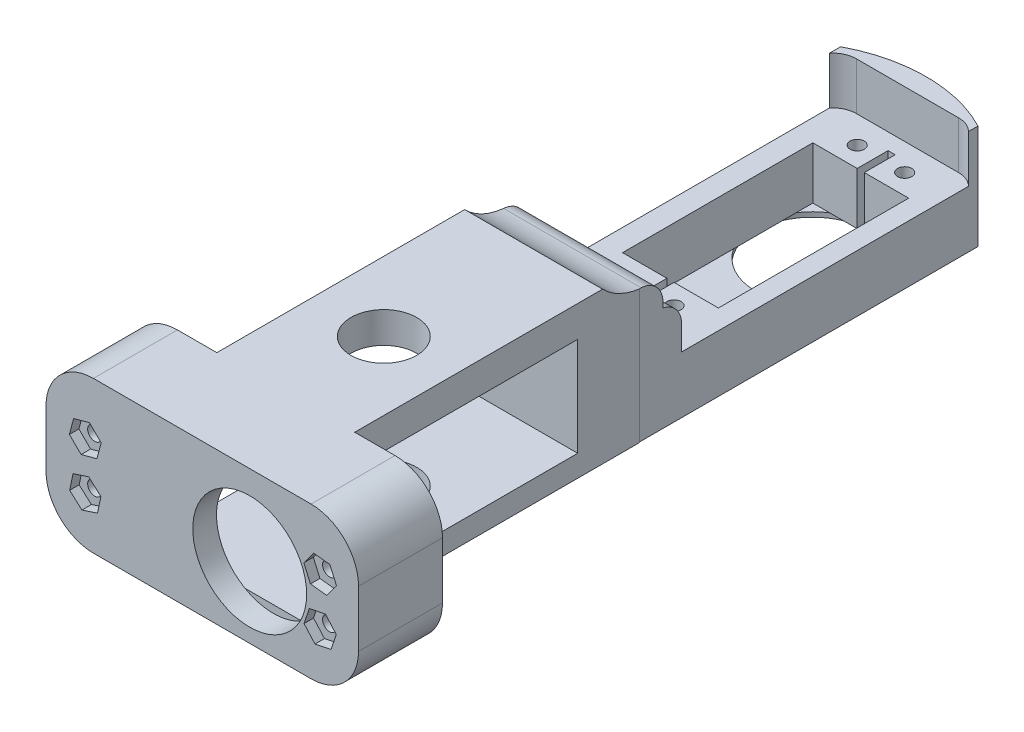
SolidWorks part; units mm, degrees
ref_plane "前视基准面" through (0, 0, 0) normal (0, 0, 1) x (1, 0, 0)
ref_plane "上视基准面" through (0, 0, 0) normal (0, 1, 0) x (1, 0, 0)
ref_plane "右视基准面" through (0, 0, 0) normal (1, 0, 0) x (0, 0, -1)
sketch "草图1" plane through (0, 0, 0) normal (0, 0, 1) x (1, 0, 0)
  line L0 (-20.4, -0.75) -> (-20.4, -10.4)
  line L1 (-30, 20) -> (30, 20)
  line L2 (-33, 17) -> (-33, -17)
  line L3 (-30, -20) -> (30, -20)
  line L4 (33, 17) -> (33, -17)
  line L5 (-33, 20) -> (33, -20) construction
  line L6 (-33, -20) -> (33, 20) construction
  line L7 (-20.4, 10.4) -> (20.4, 10.4)
  line L8 (-20.4, 10.4) -> (-20.4, 0.75)
  line L9 (-20.4, -10.4) -> (20.4, -10.4)
  line L10 (20.4, 10.4) -> (20.4, 0.75)
  line L11 (-20.4, 10.4) -> (20.4, -10.4) construction
  line L12 (-20.4, -10.4) -> (20.4, 10.4) construction
  line L13 (-28.7182, 0.75) -> (-20.4, 0.75)
  line L14 (-28.7182, 0.75) -> (-28.7182, -0.75)
  line L15 (-28.7182, -0.75) -> (-20.4, -0.75)
  line L17 (20.4, -0.75) -> (20.4, -10.4)
  line L19 (20.4, 0.75) -> (28.3856, 0.75)
  line L21 (20.4, -0.75) -> (28.3856, -0.75)
  line L22 (28.3856, 0.75) -> (28.3856, -0.75)
  arc A0 (-33, -17) -> (-30, -20) centre (-30, -17) ccw
  arc A1 (30, -20) -> (33, -17) centre (30, -17) ccw
  arc A2 (30, 20) -> (33, 17) centre (30, 17) cw
  arc A3 (-30, 20) -> (-33, 17) centre (-30, 17) ccw
  circle A4 centre (-24.65, 5.0883) radius 2.15
  circle A5 centre (-24.65, -4.9117) radius 2.15
  circle A6 centre (24.85, 5.0883) radius 2.15
  circle A7 centre (24.85, -4.9117) radius 2.15
  point P0 (0, 0)
  point P18 (0, 0)
  point P23 (-17.7766, 0.0883)
  point P28 (20.4, 0)
  dimension "D1" = 3
  dimension "D2" = 10
  dimension "D3" = 5
  dimension "D4" = 49.5
  dimension "D5" = 4.25
extrude "凸台-拉伸1" add sketch "草图1" along normal blind 12.7
sketch "草图2" plane through (0, 0, 12.7) normal (0, 0, 1) x (1, 0, 0)
  line L1 (-29.9299, 19.9398) -> (29.9299, 19.9398)
  line L2 (-32.9299, 16.9398) -> (-32.9299, -16.9398)
  line L3 (-29.9299, -19.9398) -> (29.9299, -19.9398)
  line L4 (32.9299, 16.9398) -> (32.9299, -16.9398)
  line L5 (-32.9299, 19.9398) -> (32.9299, -19.9398) construction
  line L6 (-32.9299, -19.9398) -> (32.9299, 19.9398) construction
  arc A0 (-29.9299, -19.9398) -> (-32.9299, -16.9398) centre (-29.9299, -16.9398) cw
  arc A1 (32.9299, -16.9398) -> (29.9299, -19.9398) centre (29.9299, -16.9398) cw
  arc A2 (29.9299, 19.9398) -> (32.9299, 16.9398) centre (29.9299, 16.9398) cw
  arc A3 (-29.9299, 19.9398) -> (-32.9299, 16.9398) centre (-29.9299, 16.9398) ccw
  circle A4 centre (10, 0) radius 12
  point P0 (0, 0)
  dimension "D1" = 3
  dimension "D2" = 10
extrude "凸台-拉伸3" add sketch "草图2" along normal blind 5 contours L2 A0 L3 A1 L4 A2 L1 A3 | A4
sketch "草图3" plane through (0, 0, 0) normal (0, 0, -1) x (-1, 0, 0)
  line L1 (-30, 19.9598) -> (30, 19.9598)
  line L2 (-33, 16.9598) -> (-33, -16.9598)
  line L3 (-30, -19.9598) -> (30, -19.9598)
  line L4 (33, 16.9598) -> (33, -16.9598)
  line L5 (-33, 19.9598) -> (33, -19.9598) construction
  line L6 (-33, -19.9598) -> (33, 19.9598) construction
  line L7 (-33, 10.2) -> (33, 10.2)
  line L8 (-33, 10.2) -> (-33, -10.2)
  line L9 (-33, -10.2) -> (33, -10.2)
  line L10 (33, 10.2) -> (33, -10.2)
  line L11 (-33, 10.2) -> (33, -10.2) construction
  line L12 (-33, -10.2) -> (33, 10.2) construction
  arc A0 (-33, -16.9598) -> (-30, -19.9598) centre (-30, -16.9598) ccw
  arc A1 (33, -16.9598) -> (30, -19.9598) centre (30, -16.9598) cw
  arc A2 (33, 16.9598) -> (30, 19.9598) centre (30, 16.9598) ccw
  arc A3 (-30, 19.9598) -> (-33, 16.9598) centre (-30, 16.9598) ccw
  point P1 (0, 0)
  point P18 (0, 0)
  line M14 (33, -17) -> (33, 17)
  line M18 (-33, 17) -> (-33, -17)
  line M21 (-20.4, -10.4) -> (-20.4, -0.75)
  line M25 (-20.4, 0.75) -> (-20.4, 10.4)
  line M26 (-20.4, 10.4) -> (20.4, 10.4)
  line M27 (20.4, 10.4) -> (20.4, 0.75)
  line M31 (20.4, -0.75) -> (20.4, -10.4)
  line M32 (20.4, -10.4) -> (-20.4, -10.4)
  dimension "D1" = 3
  dimension "D2" = 3
  dimension "D3" = 20.4
extrude "凸台-拉伸4" add sketch "草图3" along normal blind 50 contours L1 A3 L7 L4 A2 M18 M25 M26 M27 | A1 L9 A0 L3 M14 M31 M32 M21 M18 region at (0, 15.1159, 0) region at (0, -15.1159, 0)
sketch "草图4" plane through (0, 0, -50) normal (0, 0, -1) x (-1, 0, 0)
  line L2 (-33, 13.0402) -> (33, 13.0402)
  line L3 (-30, 19.9598) -> (30, 19.9598)
  line L4 (-33, 16.9598) -> (-33, -16.9598)
  line L5 (-30, -19.9598) -> (30, -19.9598)
  line L6 (33, 16.9598) -> (33, -16.9598)
  line L7 (-33, 19.9598) -> (33, -19.9598) construction
  line L8 (-33, -19.9598) -> (33, 19.9598) construction
  line L9 (-30, 19.9598) -> (30, 19.9598) construction
  line L10 (33, 10.2) -> (33, 16.9598) construction
  arc A0 (30, 19.9598) -> (33, 16.9598) centre (30, 16.9598) cw
  arc A1 (33, -16.9598) -> (30, -19.9598) centre (30, -16.9598) cw
  arc A2 (-33, -16.9598) -> (-30, -19.9598) centre (-30, -16.9598) ccw
  arc A3 (-30, 19.9598) -> (-33, 16.9598) centre (-30, 16.9598) ccw
  point P4 (0, 0)
  line M11 (-33, 16.9598) -> (-33, 10.2)
  line M12 (-33, 10.2) -> (-20.4, 10.2)
  line M13 (-20.4, 10.2) -> (-20.4, 10.4)
  line M14 (-20.4, 10.4) -> (20.4, 10.4)
  line M15 (20.4, 10.4) -> (20.4, 10.2)
  line M16 (20.4, 10.2) -> (33, 10.2)
  line M17 (33, 10.2) -> (33, 16.9598)
  dimension "D1" = 3
  dimension "D2" = 33
extrude "凸台-拉伸5" add sketch "草图4" along normal blind 60 and the other way blind 5 contours L4 A2 L5 A1 L6 M16 M15 M14 M13 M12 | L2 M11 M12 M13 M14 M15 M16 M17 region at (0, 11.6802, -50) region at (0, -4.7899, -50)
sketch "草图5" plane through (33, 0, 0) normal (1, 0, 0) x (0, 0, -1)
  line L0 (50, 19.9598) -> (50, 13.0402)
  line L1 (50, 19.9598) -> (60.4504, 19.9598)
  line L2 (50, 13.0402) -> (60.4504, 13.0402)
  line L3 (60.4504, 19.9598) -> (60.4504, 13.0402)
  spline S0 degree 2 poles (50, 19.9598) (53.4679, 13.8563) (60.4504, 13.0402) knots 0 0 0 1 1 1
extrude "凸台-拉伸6" add sketch "草图5" against normal blind 66 contours S0 L0 region at (33, 14.9849, -52.6781)
sketch "草图6" plane through (0, 0, -45) normal (0, 0, 1) x (1, 0, 0)
  line L0 (-29.9299, 19.9398) -> (29.9299, 19.9398) construction
  line L1 (-37.9014, 22.667) -> (37.9014, 22.667)
  line L2 (-37.9014, 22.667) -> (-37.9014, -22.667)
  line L3 (-37.9014, -22.667) -> (37.9014, -22.667)
  line L4 (37.9014, 22.667) -> (37.9014, -22.667)
  line L5 (-37.9014, 22.667) -> (37.9014, -22.667) construction
  line L6 (-37.9014, -22.667) -> (37.9014, 22.667) construction
  line L7 (-29.9299, 19.9398) -> (29.9299, 19.9398)
  line L8 (-32.9299, 16.9398) -> (-32.9299, -16.9398)
  line L9 (-29.9299, -19.9398) -> (29.9299, -19.9398)
  line L10 (32.9299, 16.9398) -> (32.9299, -16.9398)
  line L11 (-32.9299, 19.9398) -> (32.9299, -19.9398) construction
  line L12 (-32.9299, -19.9398) -> (32.9299, 19.9398) construction
  line L13 (-32.9299, 16.9398) -> (-32.9299, -16.9398) construction
  arc A0 (29.9299, 19.9398) -> (32.9299, 16.9398) centre (29.9299, 16.9398) cw
  arc A1 (32.9299, -16.9398) -> (29.9299, -19.9398) centre (29.9299, -16.9398) cw
  arc A2 (-29.9299, -19.9398) -> (-32.9299, -16.9398) centre (-29.9299, -16.9398) cw
  arc A3 (-32.9299, 16.9398) -> (-29.9299, 19.9398) centre (-29.9299, 16.9398) cw
  point P0 (0, 0)
  point P6 (0, 0)
  dimension "D1" = 3
extrude "切除-拉伸2" cut sketch "草图6" against normal blind 102
sketch "草图8" plane through (0, 13.0402, 0) normal (0, 1, 0) x (1, 0, 0)
  line L0 (-32.9299, 110) -> (32.9299, 110)
  arc A0 (-32.9299, 110) -> (32.9299, 110) centre (0, 108.1219) cw
extrude "凸台-拉伸7" add sketch "草图8" against normal blind 33
sketch "草图9" plane through (0, 13.0402, 0) normal (0, 1, 0) x (1, 0, 0)
  line L1 (-10.0231, 120.9982) -> (10.1769, 120.9982)
  line L2 (-10.0231, 120.9982) -> (-10.0231, 80.8982)
  line L3 (-10.0231, 80.8982) -> (10.1769, 80.8982)
  line L4 (10.1769, 120.9982) -> (10.1769, 80.8982)
  line L5 (-10.0231, 120.9982) -> (10.1769, 80.8982) construction
  line L6 (-10.0231, 80.8982) -> (10.1769, 120.9982) construction
  line L7 (-0.6731, 127.4982) -> (0.8269, 127.4982)
  line L8 (-0.6731, 127.4982) -> (-0.6731, 114.4982)
  line L9 (-0.6731, 114.4982) -> (0.8269, 114.4982)
  line L10 (0.8269, 127.4982) -> (0.8269, 114.4982)
  line L11 (-0.6731, 127.4982) -> (0.8269, 114.4982) construction
  line L12 (-0.6731, 114.4982) -> (0.8269, 127.4982) construction
  line L13 (-0.6731, 87.3982) -> (0.8269, 87.3982)
  line L14 (-0.6731, 87.3982) -> (-0.6731, 74.3982)
  line L15 (-0.6731, 74.3982) -> (0.8269, 74.3982)
  line L16 (0.8269, 87.3982) -> (0.8269, 74.3982)
  line L17 (-0.6731, 87.3982) -> (0.8269, 74.3982) construction
  line L18 (-0.6731, 74.3982) -> (0.8269, 87.3982) construction
  circle A0 centre (-4.9231, 125.2482) radius 2.02
  circle A1 centre (5.0769, 125.2482) radius 2.02
  circle A2 centre (-4.9231, 76.6482) radius 2.02
  circle A3 centre (5.0769, 76.6482) radius 2.02
  point P0 (0.0769, 100.9482)
  point P13 (0.0769, 120.9982)
  point P18 (0.0769, 80.8982)
  dimension "D1" = 10
  dimension "D2" = 5
  dimension "D3" = 24.3
  dimension "D4" = 24.3
  dimension "D5" = 40.1
  dimension "D6" = 1.5
  dimension "D7" = 1.5
extrude "切除-拉伸4" cut sketch "草图9" against normal blind 27 contours L13 L16 L3 L4 L1 L10 L9 L8 L2 L14 | A0 | A1 | L10 L7 L8 L1 | L10 L1 L8 L9 | L16 L13 L14 L3 | L16 L3 L14 L15 | A3 | A2 region at (0.0769, 13.0402, -100.9482) region at (0.0769, 13.0402, -124.2482) region at (0.0769, 13.0402, -117.7482) region at (0.0769, 13.0402, -84.1482) region at (0.0769, 13.0402, -77.6482) region at (-4.9231, 13.0402, -125.2482) region at (5.0769, 13.0402, -125.2482) region at (-4.9231, 13.0402, -76.6482) region at (5.0769, 13.0402, -76.6482)
sketch "草图11" plane through (0, 13.0402, 0) normal (0, 1, 0) x (1, 0, 0)
  line L1 (-10.7869, 130.9218) -> (10.7869, 130.9218)
  line L2 (-15.7869, 125.9218) -> (-15.7869, 68.999)
  line L3 (-15.7869, 68.999) -> (15.7869, 68.999)
  line L4 (15.7869, 125.9218) -> (15.7869, 68.999)
  line L5 (-15.7869, 130.9218) -> (15.7869, 68.999) construction
  line L6 (-15.7869, 68.999) -> (15.7869, 130.9218) construction
  arc A0 (-10.7869, 130.9218) -> (-15.7869, 125.9218) centre (-10.7869, 125.9218) ccw
  arc A1 (10.7869, 130.9218) -> (15.7869, 125.9218) centre (10.7869, 125.9218) cw
  point P0 (0, 99.9604)
  dimension "D1" = 5
extrude "切除-拉伸5" cut sketch "草图11" against normal blind 16
sketch "草图12" plane through (0, 13.0402, 0) normal (0, 1, 0) x (1, 0, 0)
  line L0 (-25.4565, 110.6309) -> (25.4565, 110.6309)
  line L1 (-25.4565, 110.6309) -> (25.4565, 110.6309)
  line L2 (-25.4565, 110.6309) -> (-25.4565, 65.0871)
  line L3 (-25.4565, 65.0871) -> (25.4565, 65.0871)
  line L4 (25.4565, 110.6309) -> (25.4565, 65.0871)
  line L5 (-25.4565, 110.6309) -> (25.4565, 65.0871) construction
  line L6 (-25.4565, 65.0871) -> (25.4565, 110.6309) construction
  arc A0 (-25.4565, 110.6309) -> (25.4565, 110.6309) centre (0, 110.6309) cw
  point P0 (0, 87.859)
  arc M5 (10.7869, 130.9218) -> (15.7869, 125.9218) centre (10.7869, 125.9218) cw
  line M6 (15.7869, 125.9218) -> (15.7869, 68.999)
  line M7 (15.7869, 68.999) -> (-15.7869, 68.999)
  line M8 (-15.7869, 68.999) -> (-15.7869, 125.9218)
  arc M9 (-15.7869, 125.9218) -> (-10.7869, 130.9218) centre (-10.7869, 125.9218) cw
  line M10 (-10.7869, 130.9218) -> (10.7869, 130.9218)
extrude "切除-拉伸7" cut sketch "草图12" against normal blind 6 contours L4 L0 L2 L3 M6 M7 M8 | A0 L0 M8 M9 M10 M5 M6 region at (0, 13.0402, -135.5181) region at (-20.6217, 13.0402, -109.9478)
sketch "草图13" plane through (0, -13.9598, 0) normal (0, 1, 0) x (1, 0, 0)
  line L0 (0.8269, 80.8982) -> (10.1769, 80.8982) construction
  circle A0 centre (0, 110.8982) radius 12
  dimension "D1" = 30
extrude "切除-拉伸8" cut sketch "草图13" against normal blind 80
sketch "草图14" plane through (0, 0, 17.7) normal (0, 0, 1) x (1, 0, 0)
  line L0 (-29.9299, 19.9398) -> (29.9299, 19.9398) construction
  line L1 (-29.9299, 19.9398) -> (29.9299, 19.9398)
  line L2 (-32.9299, 16.9398) -> (-32.9299, -16.9398)
  line L3 (-29.9299, -19.9398) -> (29.9299, -19.9398)
  line L4 (32.9299, 16.9398) -> (32.9299, -16.9398)
  line L5 (-32.9299, 19.9398) -> (32.9299, -19.9398) construction
  line L6 (-32.9299, -19.9398) -> (32.9299, 19.9398) construction
  line L7 (-32.9299, 16.9398) -> (-32.9299, -16.9398) construction
  line L9 (-36.1294, 24.0704) -> (36.1294, 24.0704)
  line L10 (-36.1294, 24.0704) -> (-36.1294, -24.0704)
  line L11 (-36.1294, -24.0704) -> (36.1294, -24.0704)
  line L12 (36.1294, 24.0704) -> (36.1294, -24.0704)
  line L13 (-36.1294, 24.0704) -> (36.1294, -24.0704) construction
  line L14 (-36.1294, -24.0704) -> (36.1294, 24.0704) construction
  arc A0 (29.9299, 19.9398) -> (32.9299, 16.9398) centre (29.9299, 16.9398) cw
  arc A1 (29.9299, -19.9398) -> (32.9299, -16.9398) centre (29.9299, -16.9398) ccw
  arc A2 (-29.9299, -19.9398) -> (-32.9299, -16.9398) centre (-29.9299, -16.9398) cw
  arc A3 (-29.9299, 19.9398) -> (-32.9299, 16.9398) centre (-29.9299, 16.9398) ccw
  point P0 (0, 0)
  point P22 (0, 0)
  dimension "D1" = 3
extrude "切除-拉伸9" cut sketch "草图14" against normal blind 146
sketch "草图15" plane through (0, 0, 17.7) normal (0, 0, 1) x (1, 0, 0)
  line L1 (-27, 15) -> (27, 15)
  line L2 (-30, 12) -> (-30, -12)
  line L3 (-27, -15) -> (27, -15)
  line L4 (30, 12) -> (30, -12)
  line L5 (-30, 15) -> (30, -15) construction
  line L6 (-30, -15) -> (30, 15) construction
  line L7 (-36.3575, 21.962) -> (36.3575, 21.962)
  line L8 (-36.3575, 21.962) -> (-36.3575, -21.962)
  line L9 (-36.3575, -21.962) -> (36.3575, -21.962)
  line L10 (36.3575, 21.962) -> (36.3575, -21.962)
  line L11 (-36.3575, 21.962) -> (36.3575, -21.962) construction
  line L12 (-36.3575, -21.962) -> (36.3575, 21.962) construction
  arc A0 (27, 15) -> (30, 12) centre (27, 12) cw
  arc A1 (30, -12) -> (27, -15) centre (27, -12) cw
  arc A2 (-27, -15) -> (-30, -12) centre (-27, -12) cw
  arc A3 (-30, 12) -> (-27, 15) centre (-27, 12) cw
  point P0 (0, 0)
  point P18 (0, 0)
  dimension "D1" = 3
sketch "草图18" plane through (0, 0, 0) normal (0, 0, -1) x (-1, 0, 0)
  circle A0 centre (-24.85, 5.0883) radius 2.15
  circle A1 centre (-24.85, 5.0883) radius 2.15 construction
  circle A2 centre (-24.85, 5.0883) radius 1.5
  circle A3 centre (-24.85, -4.9117) radius 2.15
  circle A4 centre (-24.85, -4.9117) radius 2.15 construction
  circle A5 centre (-24.85, -4.9117) radius 1.5
  circle A6 centre (24.65, 5.0883) radius 2.15
  circle A7 centre (24.65, 5.0883) radius 1.5
  circle A8 centre (24.65, -4.9117) radius 2.15
  circle A9 centre (24.65, -4.9117) radius 1.5
extrude "凸台-拉伸8" add sketch "草图18" against normal blind 14
sketch "草图19" plane through (0, 0, 0) normal (0, 0, -1) x (-1, 0, 0)
  circle A0 centre (-24.85, 5.0883) radius 1.5
  circle A1 centre (-24.85, -4.9117) radius 1.5
  circle A2 centre (24.65, 5.0883) radius 1.5
  circle A3 centre (24.65, -4.9117) radius 1.5
extrude "切除-拉伸14" cut sketch "草图19" against normal blind 25
sketch "草图21" plane through (0, 13.0402, 0) normal (0, 1, 0) x (1, 0, 0)
  line L0 (-41.7762, 142.5299) -> (39.2123, 142.5299)
  line L1 (-41.7762, 142.5299) -> (-41.7762, 60.0333)
  line L2 (39.2123, 142.5299) -> (39.2123, 60.0333)
  line L3 (-41.7762, 60.0333) -> (39.2123, 60.0333)
  line L4 (-14.6296, 60.0333) -> (-14.6296, 131.4637)
  line L5 (-14.6296, 60.0333) -> (14.3193, 60.0333)
  line L7 (14.3193, 60.0333) -> (14.3193, 131.4637)
  arc A0 (25.4565, 110.6309) -> (-25.4565, 110.6309) centre (0, 110.6309) ccw construction
  arc A1 (-14.6296, 131.4637) -> (14.3193, 131.4637) centre (-0.1552, 103.7858) cw
  line M5 (25.4565, 110.6309) -> (25.4565, 65.0871)
  line M6 (25.4565, 65.0871) -> (-25.4565, 65.0871)
  line M7 (-25.4565, 65.0871) -> (-25.4565, 110.6309)
  arc M8 (-25.4565, 110.6309) -> (25.4565, 110.6309) centre (0, 110.6309) cw
  arc M10 (32.9299, 110) -> (-32.9299, 110) centre (0, 108.1219) ccw
  line M12 (-32.9299, 60.4504) -> (32.9299, 60.4504)
extrude "切除-拉伸17" cut sketch "草图21" against normal blind 39 contours L7 L4 M12 M10 M6 M7 M8 M5 | L4 M6 M8 M7 | L7 L3 L2 L0 L1 L4 M12 M10 | A1 L7 M8 M6 M5 region at (-1.2819, 13.0402, -141.3738) region at (-19.8019, 13.0402, -95.3565) region at (19.0175, 13.0402, -96.7175)
sketch "草图24" plane through (0, 19.9398, 0) normal (0, 1, 0) x (1, 0, 0)
  line L0 (-14.6296, 60.4504) -> (-29.9299, 0)
  line L1 (-29.9299, -17.7) -> (-29.9299, 50.0114) construction
  line L2 (-29.9299, 0) -> (-48.0566, 0)
  line L3 (-48.0566, 0) -> (-48.0566, 60.4504)
  line L4 (-48.0566, 60.4504) -> (-14.6296, 60.4504)
  line L5 (14.3193, 60.4504) -> (58.3545, 60.4504)
  line L6 (58.3545, 60.4504) -> (58.3545, 0)
  line L7 (58.3545, 0) -> (29.9299, 0)
  line L8 (29.9299, -17.7) -> (29.9299, 50.0114) construction
  line L9 (29.9299, 0) -> (14.3193, 60.4504)
extrude "切除-拉伸22" cut sketch "草图24" against normal blind 102
sketch "草图25" plane through (-32.9299, 0, 0) normal (-1, 0, 0) x (0, 0, 1)
  line L0 (-45, 10.4) -> (-45, -10.4)
  line L1 (-45, 10.4) -> (-47, 10.4)
  line L2 (-45, -10.4) -> (-47, -10.4)
  line L3 (-47, 10.4) -> (-47, -10.4)
extrude "切除-拉伸23" cut sketch "草图25" against normal blind 102
sketch "草图26" plane through (-14.6296, 0, 0) normal (-1, 0, 0) x (0, 0, 1)
  line L0 (-135.02, -19.9598) -> (20.7531, -19.9598)
  line L1 (-135.02, -19.9598) -> (-135.02, -17.9598)
  line L2 (20.7531, -19.9598) -> (20.7531, -17.9598)
  line L3 (-135.02, -17.9598) -> (20.7531, -17.9598)
extrude "切除-拉伸27" cut sketch "草图26" against normal blind 102 and the other way blind 102
sketch "草图27" plane through (0, -2.9598, 0) normal (0, 1, 0) x (1, 0, 0)
  circle A0 centre (-4.9231, 125.2482) radius 2.02
  circle A1 centre (-4.9231, 125.2482) radius 1.5
  circle A2 centre (5.0769, 125.2482) radius 2.02
  circle A3 centre (5.0769, 125.2482) radius 1.5
  circle A4 centre (5.0769, 76.6482) radius 2.02
  circle A5 centre (5.0769, 76.6482) radius 1.5
  circle A6 centre (-4.9231, 76.6482) radius 2.02
  circle A7 centre (-4.9231, 76.6482) radius 1.5
extrude "凸台-拉伸9" add sketch "草图27" against normal blind 15
sketch "草图28" plane through (0, -2.9598, 0) normal (0, 1, 0) x (1, 0, 0)
  circle A0 centre (-4.9231, 125.2482) radius 1.5
  circle A1 centre (5.0769, 125.2482) radius 1.5
  circle A2 centre (5.0769, 76.6482) radius 1.5
  circle A3 centre (-4.9231, 76.6482) radius 1.5
extrude "切除-拉伸30" cut sketch "草图28" against normal blind 22
sketch "草图29" plane through (14.3193, 0, 0) normal (1, 0, 0) x (0, 0, -1)
  line L0 (-30.1806, -37.6079) -> (143.7443, -37.6079)
  line L1 (-30.1806, -37.6079) -> (-30.1806, -14.9598)
  line L2 (143.7443, -37.6079) -> (143.7443, -14.9598)
  line L3 (-30.1806, -14.9598) -> (143.7443, -14.9598)
  line L4 (60.0333, -17.9598) -> (131.4637, -17.9598) construction
  dimension "D1" = 3
extrude "切除-拉伸31" cut sketch "草图29" against normal blind 58 and the other way blind 58
sketch "草图31" plane through (0, 19.9398, 0) normal (0, 1, 0) x (1, 0, 0)
  circle A0 centre (0, 20.5577) radius 6.9277
extrude "切除-拉伸32" cut sketch "草图31" against normal blind 58
sketch "草图32" plane through (0, -14.9598, 0) normal (0, -1, 0) x (1, 0, 0)
  line L1 (-2.6333, -79.2476) -> (-1.527, -75.9649)
  line L2 (-1.527, -75.9649) -> (-3.8167, -73.3655)
  line L3 (-3.8167, -73.3655) -> (-7.2128, -74.0487)
  line L4 (-7.2128, -74.0487) -> (-8.3191, -77.3314)
  line L5 (-8.3191, -77.3314) -> (-6.0294, -79.9309)
  line L6 (-6.0294, -79.9309) -> (-2.6333, -79.2476)
  line L7 (7.0787, -79.4754) -> (8.5262, -76.3282)
  line L8 (8.5262, -76.3282) -> (6.5245, -73.501)
  line L9 (6.5245, -73.501) -> (3.0752, -73.821)
  line L10 (3.0752, -73.821) -> (1.6276, -76.9682)
  line L11 (1.6276, -76.9682) -> (3.6294, -79.7953)
  line L12 (3.6294, -79.7953) -> (7.0787, -79.4754)
  line L13 (-2.1812, -123.131) -> (-5.3857, -121.8151)
  line L14 (-5.3857, -121.8151) -> (-8.1275, -123.9323)
  line L15 (-8.1275, -123.9323) -> (-7.6649, -127.3653)
  line L16 (-7.6649, -127.3653) -> (-4.4605, -128.6813)
  line L17 (-4.4605, -128.6813) -> (-1.7186, -126.5641)
  line L18 (-1.7186, -126.5641) -> (-2.1812, -123.131)
  line L19 (7.864, -127.3055) -> (8.2521, -123.8632)
  line L20 (8.2521, -123.8632) -> (5.4651, -121.8059)
  line L21 (5.4651, -121.8059) -> (2.2899, -123.1909)
  line L22 (2.2899, -123.1909) -> (1.9018, -126.6332)
  line L23 (1.9018, -126.6332) -> (4.6888, -128.6905)
  line L24 (4.6888, -128.6905) -> (7.864, -127.3055)
  circle A0 centre (-4.9231, -76.6482) radius 3 construction
  circle A1 centre (5.0769, -76.6482) radius 3 construction
  circle A2 centre (-4.9231, -125.2482) radius 3 construction
  circle A3 centre (5.0769, -125.2482) radius 3 construction
extrude "切除-拉伸33" cut sketch "草图32" against normal blind 2
sketch "草图33" plane through (0, 0, 17.7) normal (0, 0, 1) x (1, 0, 0)
  line L1 (-22.1935, 2.6458) -> (-21.3065, 5.9944)
  line L2 (-21.3065, 5.9944) -> (-23.763, 8.4369)
  line L3 (-23.763, 8.4369) -> (-27.1065, 7.5308)
  line L4 (-27.1065, 7.5308) -> (-27.9935, 4.1822)
  line L5 (-27.9935, 4.1822) -> (-25.537, 1.7397)
  line L6 (-25.537, 1.7397) -> (-22.1935, 2.6458)
  line L7 (-22.0694, -7.2227) -> (-21.3584, -3.8323)
  line L8 (-21.3584, -3.8323) -> (-23.939, -1.5214)
  line L9 (-23.939, -1.5214) -> (-27.2306, -2.6008)
  line L10 (-27.2306, -2.6008) -> (-27.9416, -5.9911)
  line L11 (-27.9416, -5.9911) -> (-25.361, -8.3021)
  line L12 (-25.361, -8.3021) -> (-22.0694, -7.2227)
  line L13 (26.2425, 1.9164) -> (28.2932, 4.7082)
  line L14 (28.2932, 4.7082) -> (26.9007, 7.8801)
  line L15 (26.9007, 7.8801) -> (23.4575, 8.2602)
  line L16 (23.4575, 8.2602) -> (21.4068, 5.4683)
  line L17 (21.4068, 5.4683) -> (22.7993, 2.2964)
  line L18 (22.7993, 2.2964) -> (26.2425, 1.9164)
  line L19 (27.1493, -7.5027) -> (28.2435, -4.216)
  line L20 (28.2435, -4.216) -> (25.9443, -1.625)
  line L21 (25.9443, -1.625) -> (22.5507, -2.3207)
  line L22 (22.5507, -2.3207) -> (21.4565, -5.6074)
  line L23 (21.4565, -5.6074) -> (23.7557, -8.1985)
  line L24 (23.7557, -8.1985) -> (27.1493, -7.5027)
  circle A0 centre (-24.65, 5.0883) radius 3 construction
  circle A1 centre (-24.65, -4.9117) radius 3 construction
  circle A2 centre (24.85, 5.0883) radius 3 construction
  circle A3 centre (24.85, -4.9117) radius 3 construction
extrude "切除-拉伸34" cut sketch "草图33" against normal blind 2
sketch "草图34" plane through (0, 19.9398, 0) normal (0, 1, 0) x (1, 0, 0)
  line L0 (-14.6296, 60.4504) -> (-14.6296, 0)
  line L1 (-14.6296, 60.4504) -> (-46.7743, 60.4504)
  line L2 (-14.6296, 0) -> (-46.7743, 0)
  line L3 (-46.7743, 60.4504) -> (-46.7743, 0)
  line L4 (14.427, 60.0333) -> (14.427, 0)
  line L5 (14.427, 60.0333) -> (44.969, 60.0333)
  line L6 (14.427, 0) -> (44.969, 0)
  line L7 (44.969, 60.0333) -> (44.969, 0)
extrude "切除-拉伸35" cut sketch "草图34" against normal blind 69
sketch "草图35" plane through (14.427, 0, 0) normal (1, 0, 0) x (0, 0, -1)
  line L0 (-17.7, 16.9398) -> (61.4806, 16.9398)
  line L1 (-17.7, 16.9398) -> (-17.7, 23.8144)
  line L2 (61.4806, 16.9398) -> (61.4806, 23.8144)
  line L3 (-17.7, 23.8144) -> (61.4806, 23.8144)
extrude "切除-拉伸36" cut sketch "草图35" against normal blind 69 and the other way blind 69
fillet "圆角1" radius 10 4 edges at (-32.9299, -14.9598, 8.85) (32.9299, -14.9598, 8.85) (32.9299, 16.9398, 8.85) (-32.9299, 16.9398, 8.85)
fillet "圆角3" radius 5 2 edges at (-0.1552, 13.0402, -65.0871) (-0.1552, 7.0402, -68.999)
